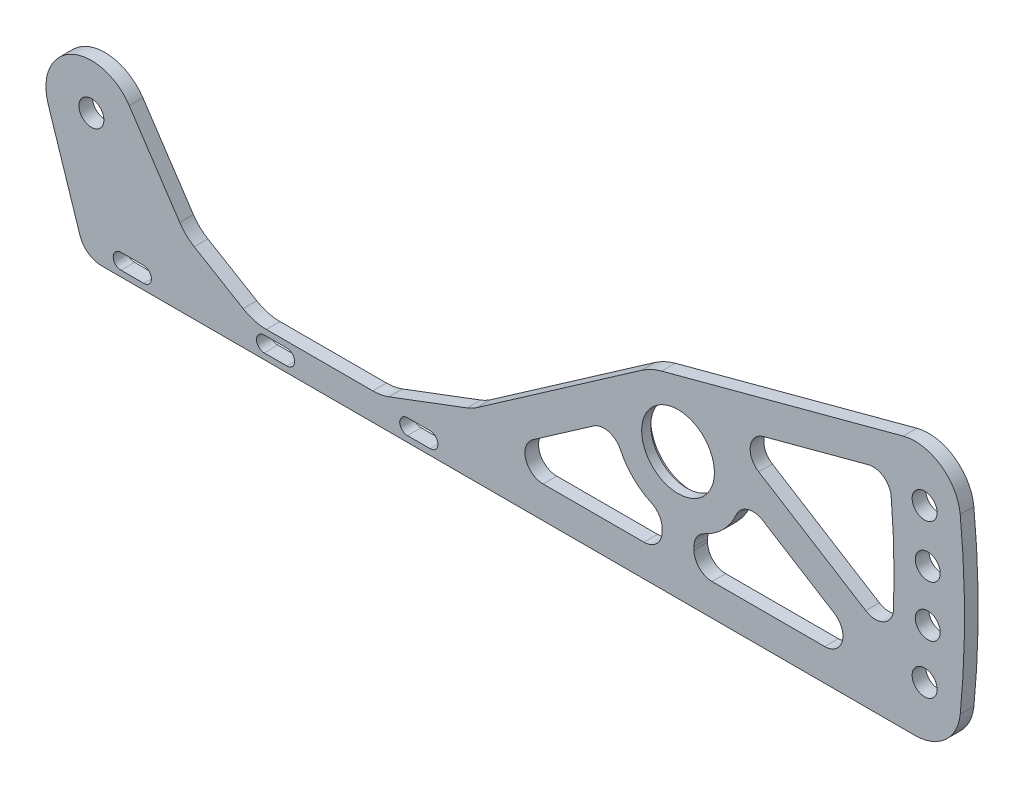
SolidWorks part; units mm, degrees
ref_plane "Спереди" through (0, 0, 0) normal (0, 0, 1) x (1, 0, 0)
ref_plane "Сверху" through (0, 0, 0) normal (0, 1, 0) x (1, 0, 0)
ref_plane "Справа" through (0, 0, 0) normal (1, 0, 0) x (0, 0, -1)
sketch "Эскиз1" plane through (0, 0, 0) normal (0, 0, 1) x (1, 0, 0)
  line L0 (-31.9542, -25) -> (253.1565, -25) construction
  line L1 (9, 35.6094) -> (9, -47.5785) construction
  line L2 (-39.2405, -28) -> (262.4545, -28) construction
  line L3 (-31.9542, -22) -> (262.4545, -22) construction
  line L4 (-9.5085, -3.0964) -> (-1.3987, -28)
  line L5 (8.3266, 5.5379) -> (20.6752, -13.0291)
  line L6 (-26.4187, 0) -> (187.6558, 0) construction
  line L7 (121.0002, 11.4893) -> (83.7656, -14.4365)
  line L8 (63.7181, -22) -> (35.7314, -22)
  line L9 (0, 0) -> (183.9142, 5.6191) construction
  line L10 (0, 0) -> (183.9142, -5.6191) construction
  line L11 (0, 0) -> (183.2281, -16.8363) construction
  line L12 (0, 0) -> (183.2281, 16.8363) construction
  line L13 (125.388, 13.526) -> (189.5368, 30.6561)
  line L14 (-1.3987, -28) -> (189.9474, -28)
  line L15 (40.5, -17.0585) -> (40.5, -35.954) construction
  line L16 (72, -17.0585) -> (72, -35.954) construction
  line L17 (20.6752, -13.0291) -> (35.7314, -22)
  line L18 (83.7656, -14.4365) -> (63.7181, -22)
  arc A0 (8.3266, 5.5379) -> (-9.5085, -3.0964) centre (0, 0) ccw
  circle A1 centre (129, 0) radius 8
  arc A2 (125.388, 13.526) -> (121.0002, 11.4893) centre (129, 0) ccw
  circle A3 centre (0, 0) radius 184 construction
  arc A4 (189.9474, -28) -> (189.5368, 30.6561) centre (0, 0) ccw
  dimension "D1" = 20
  dimension "D2" = 25
  dimension "D3" = 9
  dimension "D6" = 16
  dimension "D8" = 28
  dimension "D9" = 368
  dimension "D10" = 31.5
  dimension "D16" = 192
  dimension "D4" = 6
  dimension "D5" = 3
  dimension "D7" = 129
  dimension "D11" = 3.5
  dimension "D12" = 3.5
  dimension "D13" = 3.5
  dimension "D14" = 1.75
  dimension "D15" = 31.5
extrude "Бобышка-Вытянуть1" add sketch "Эскиз1" along normal blind 3
hole_wizard "Отверстие с зазором M31" positions "Эскиз3" profile "Эскиз2" hole size "M3" standard "Ansi Metric" end condition through all
sketch "Эскиз3" plane through (0, 0, 3) normal (0, 0, 1) x (1, 0, 0)
  line L0 (-31.9542, -25) -> (253.1565, -25) construction
  line L1 (9, 35.6094) -> (9, -47.5785) construction
  line L2 (40.5, -17.0585) -> (40.5, -35.954) construction
  line L3 (72, -17.0585) -> (72, -35.954) construction
  point P0 (9, -25)
  point P6 (40.5, -25)
  point P10 (72, -25)
sketch "Эскиз2" plane through (9, -25, 3) normal (1, 0, 0) x (0, -1, 0)
  line L0 (0, 0) -> (0, 3)
  line L1 (0, 3) -> (1.7, 3)
  line L2 (1.7, 3) -> (1.7, 0)
  line L5 (1.7, 0) -> (0, 0)
  line L11 (0, -6.35) -> (0, 107.95) construction
  dimension "Диаметр сквозного отверстия" = 3.4
  dimension "Глубина сквозного отверстия" = 3
hole_wizard "Отверстие с зазором M51" positions "Эскиз5" profile "Эскиз4" hole size "M5" standard "Ansi Metric" end condition through all
sketch "Эскиз5" plane through (0, 0, 3) normal (0, 0, 1) x (1, 0, 0)
  point P2 (0, 0)
sketch "Эскиз4" plane through (0, 0, 3) normal (1, 0, 0) x (0, -1, 0)
  line L0 (0, 0) -> (0, 3)
  line L1 (0, 3) -> (2.75, 3)
  line L2 (2.75, 3) -> (2.75, 0)
  line L5 (2.75, 0) -> (0, 0)
  line L11 (0, -6.35) -> (0, 107.95) construction
  dimension "Диаметр сквозного отверстия" = 5.5
  dimension "Глубина сквозного отверстия" = 3
hole_wizard "Отверстие с зазором M52" positions "Эскиз7" profile "Эскиз6" hole size "M5" standard "Ansi Metric" end condition through all
sketch "Эскиз7" plane through (0, 0, 3) normal (0, 0, 1) x (1, 0, 0)
  point P0 (183.2281, 16.8363)
  point P3 (183.9142, 5.6191)
  point P6 (183.9142, -5.6191)
  point P9 (183.2281, -16.8363)
sketch "Эскиз6" plane through (183.2281, 16.8363, 3) normal (1, 0, 0) x (0, -1, 0)
  line L0 (0, 0) -> (0, 3)
  line L1 (0, 3) -> (2.75, 3)
  line L2 (2.75, 3) -> (2.75, 0)
  line L5 (2.75, 0) -> (0, 0)
  line L11 (0, -6.35) -> (0, 107.95) construction
  dimension "Диаметр сквозного отверстия" = 5.5
  dimension "Глубина сквозного отверстия" = 3
fillet "Скругление1" radius 10 6 edges at (35.7314, -22, 1.5) (20.6752, -13.0291, 1.5) (63.7181, -22, 1.5) (83.7656, -14.4365, 1.5) (189.9474, -28, 1.5) (189.5368, 30.6561, 1.5)
fillet "Скругление2" radius 5 1 edges at (-1.3987, -28, 1.5)
sketch "Эскиз8" plane through (0, 0, 3) normal (0, 0, 1) x (1, 0, 0)
  line L0 (138.9079, 9.8911) -> (175.4042, 19.6369)
  line L1 (178.5224, 27.7149) -> (125.388, 13.526) construction
  line L2 (142.9717, -0.889) -> (175.2463, -21)
  line L3 (175.2463, -21) -> (132.5, -21)
  line L4 (2.2315, -28) -> (181.1077, -28) construction
  line L5 (115.0501, -1.1834) -> (86.5894, -21)
  line L6 (121.0002, 11.4893) -> (84.7863, -13.7258) construction
  line L8 (125.5, -13.5554) -> (125.5, -21)
  line L9 (132.5, -13.5554) -> (132.5, -21)
  line L10 (138.9079, 9.8911) -> (176.0039, -13.2243)
  line L11 (125.5, -21) -> (86.5894, -21)
  arc A0 (115.0501, -1.1834) -> (125.5, -13.5554) centre (129, 0) ccw
  arc A1 (125.388, 13.526) -> (121.0002, 11.4893) centre (129, 0) ccw construction
  arc A2 (176.0039, -13.2243) -> (175.4042, 19.6369) centre (0, 0) ccw
  arc A3 (132.5, -13.5554) -> (142.9717, -0.889) centre (129, 0) ccw
  dimension "D2" = 353
  dimension "D1" = 7
  dimension "D3" = 7
  dimension "D4" = 7
  dimension "D5" = 7
  dimension "D6" = 3.5
  dimension "D7" = 7
extrude "Вырез-Вытянуть1" cut sketch "Эскиз8" against normal through all
fillet "Скругление3" radius 4 11 edges at (86.5894, -21, 1.5) (125.5, -21, 1.5) (115.0501, -1.1834, 1.5) (125.5, -13.5554, 1.5) (132.5, -21, 1.5) (132.5, -13.5554, 1.5) (142.9717, -0.889, 1.5) (175.2463, -21, 1.5) (176.0039, -13.2243, 1.5) (175.4042, 19.6369, 1.5) (138.9079, 9.8911, 1.5)
sketch "Эскиз9" plane through (0, 0, 0) normal (0, 0, -1) x (-1, 0, 0)
  circle A0 centre (-129, 0) radius 9
  dimension "D1" = 18
extrude "Вырез-Вытянуть2" cut sketch "Эскиз9" against normal blind 1
sketch "Эскиз10" plane through (0, 0, 3) normal (0, 0, 1) x (1, 0, 0)
  line L0 (6.5, -25) -> (11.5, -25) construction
  line L1 (6.5, -23.3) -> (11.5, -23.3)
  line L2 (6.5, -26.7) -> (11.5, -26.7)
  line L3 (38, -25) -> (43, -25) construction
  line L4 (38, -23.3) -> (43, -23.3)
  line L5 (38, -26.7) -> (43, -26.7)
  line L6 (69.5, -25) -> (74.5, -25) construction
  line L7 (69.5, -23.3) -> (74.5, -23.3)
  line L8 (69.5, -26.7) -> (74.5, -26.7)
  arc A0 (6.5, -23.3) -> (6.5, -26.7) centre (6.5, -25) ccw
  arc A1 (11.5, -26.7) -> (11.5, -23.3) centre (11.5, -25) ccw
  circle A2 centre (9, -25) radius 1.7 construction
  arc A3 (38, -23.3) -> (38, -26.7) centre (38, -25) ccw
  arc A4 (43, -26.7) -> (43, -23.3) centre (43, -25) ccw
  circle A5 centre (40.5, -25) radius 1.7 construction
  arc A6 (69.5, -23.3) -> (69.5, -26.7) centre (69.5, -25) ccw
  arc A7 (74.5, -26.7) -> (74.5, -23.3) centre (74.5, -25) ccw
  circle A8 centre (72, -25) radius 1.7 construction
  point P2 (9, -25)
  point P12 (40.5, -25)
  point P22 (72, -25)
  dimension "D1" = 5
  dimension "D2" = 5
  dimension "D3" = 5
extrude "Вырез-Вытянуть3" cut sketch "Эскиз10" against normal through all
sketch "Эскиз11" plane through (0, 0, 0) normal (0, 0, 1) x (1, 0, 0)
  line L0 (192, 41.8956) -> (192, -28) construction
  line L1 (192, -28) -> (188.2804, -28) construction
  line L2 (2.2315, -28) -> (181.1077, -28) construction
  line L3 (-10, 21.326) -> (-10, -31.1704) construction
  line L4 (142.753, 28.0534) -> (192, 28.0534) construction
  arc A0 (191.0587, -18.989) -> (191.0531, 19.0454) centre (0, 0) ccw construction
  arc A1 (8.3266, 5.5379) -> (-9.5085, -3.0964) centre (0, 0) ccw construction
  arc A2 (191.0531, 19.0454) -> (178.5224, 27.7149) centre (181.1024, 18.0534) ccw construction
equation "\"D12@Эскиз1\"=\"D11@Эскиз1\""
equation "\"D13@Эскиз1\"=\"D11@Эскиз1\""
equation "\"D14@Эскиз1\"=\"D11@Эскиз1\"/2"
